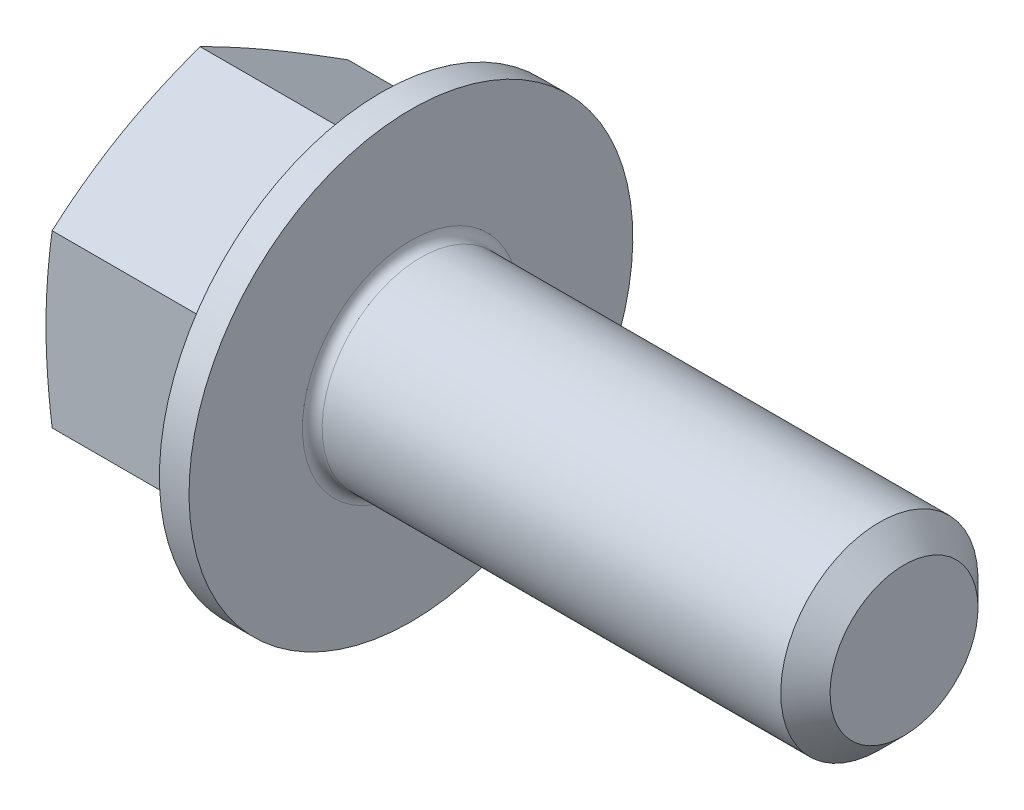
SolidWorks part; units mm, degrees
ref_plane "Front Plane" through (0, 0, 0) normal (0, 0, 1) x (1, 0, 0)
ref_plane "Top Plane" through (0, 0, 0) normal (0, 1, 0) x (1, 0, 0)
ref_plane "Right Plane" through (0, 0, 0) normal (1, 0, 0) x (0, 0, -1)
sketch "Sketch1" plane through (0, 0, 0) normal (0, 0, 1) x (1, 0, 0)
  line L0 (0, 0) -> (5, 0) construction
  line L1 (0, 0) -> (-2.2, 0) construction
  line L2 (0.1, 1) -> (4.75, 1)
  line L3 (5, 0) -> (5, 0.75)
  line L4 (0, 1.1) -> (0, 2.25)
  line L5 (0, 2.25) -> (-0.3, 2.25)
  line L6 (-0.3, 2.25) -> (-0.501, 1.5)
  line L7 (-0.501, 1.5) -> (-2.2, 1.5)
  line L8 (-2.2, 1.5) -> (-2.2, 1.2)
  line L9 (-2.2, 1.2) -> (-1.925, 1.2)
  line L10 (-1.925, 1.2) -> (-1.925, 0)
  line L11 (-1.925, 0) -> (5, 0)
  line L12 (-1.925, 0) -> (-1.925, 1.58) construction
  line L14 (5, 0.75) -> (4.75, 1)
  line L15 (5, 0) -> (0.4, 0) construction
  arc A0 (0.1, 1) -> (0, 1.1) centre (0.1, 1.1) cw
  dimension "D7" = 0.1
  dimension "L" = 5
  dimension "K" = 2.2
  dimension "s" = 3
  dimension "dia" = 2
  dimension "D1" = 2.4
  dimension "D2" = 0.275
  dimension "c" = 0.3
  dimension "D4" = 15
  dimension "D5" = 45
  dimension "min" = 1.5
  dimension "B" = 4.6
  dimension "Dc" = 4.5
revolve "Revolve1" add sketch "Sketch1" angle 360 about L11
cosmetic thread "Cosmetic Thread1" [suppressed] parameters "D1"=4.25, "D2"=1.5
sketch "Sketch2" plane through (-2.2, 0, 0) normal (-1, 0, 0) x (0, 0, 1)
  line L1 (0, 1.7321) -> (-1.5, 0.866)
  line L2 (-1.5, 0.866) -> (-1.5, -0.866)
  line L3 (-1.5, -0.866) -> (0, -1.7321)
  line L4 (0, -1.7321) -> (1.5, -0.866)
  line L5 (1.5, -0.866) -> (1.5, 0.866)
  line L6 (1.5, 0.866) -> (0, 1.7321)
  circle A0 centre (0, 0) radius 1.2 construction
  circle A1 centre (0, 0) radius 1.2
  circle A2 centre (0, 0) radius 1.5 construction
  circle A3 centre (0, 0) radius 1.5 construction
extrude "Extrude1" add sketch "Sketch2" against normal up to next (2.2 mm away)
sketch "Sketch3" plane through (0, 0, 0) normal (0, 1, 0) x (1, 0, 0)
  line L0 (-2.401, 0.75) -> (-1.999, 2.25)
  line L1 (-2.2, 0) -> (-2.2, 1.5) construction
  line L2 (0, 0) -> (-3.6033, 0) construction
  line L3 (-1.999, 2.25) -> (-2.401, 2.25)
  line L4 (-2.401, 2.25) -> (-2.401, 0.75)
  dimension "D1" = 15
  dimension "D2" = 1.5
revolve "Cut-Revolve1" cut sketch "Sketch3" angle 360 about L2
fillet "Fillet1" radius 0.1 6 edges
sketch "Sketch4" plane through (0, 0, 0) normal (0, 0, 1) x (1, 0, 0)
  line L0 (0, 0) -> (5.3731, 0) construction
  line L1 (5, -0.75) -> (5, 0.75) construction
  line L3 (5, 0.665) -> (4.1912, 1)
  line L4 (0.1, 1) -> (4.75, 1) construction
  line L5 (4.1912, 1) -> (4.1912, 1.5)
  line L6 (4.1912, 1.5) -> (5, 1.5)
  line L7 (5, 1.5) -> (5, 0.665)
  dimension "D1" = 0.5
  dimension "D2" = 22.5
  dimension "Dp" = 1.33
revolve "Cut-Revolve2" [suppressed] cut sketch "Sketch4" angle 360 about L0
sketch "Sketch5" plane through (0, 0, 0) normal (0, 0, 1) x (1, 0, 0)
  line L0 (5, 0) -> (0.75, 0) construction
  line L1 (-1.925, 0) -> (5, 0) construction
  line L2 (0.8943, 0.75) -> (1.0387, 1)
  line L3 (1.0387, 1) -> (1.0387, 1.2887)
  line L4 (1.0387, 1.2887) -> (0.75, 1.2887)
  line L5 (0.75, 1.2887) -> (0.75, 1)
  line L6 (0.75, 1) -> (0.8943, 0.75)
  dimension "B" = 4.25
  dimension "D1" = 1.5
  dimension "D2" = 2
revolve "Cut-Revolve10" [suppressed] cut sketch "Sketch5" angle 360 about L0
pattern_linear "LPattern10" [suppressed] count 11 spacing 0.4 along (1, 0, 0) of bodies 111
equation "\"D1@Sketch1\" = \"s@Sketch1\" / 10 * 8"
equation "\"D2@Sketch1\" = \"K@Sketch1\" / 8"
equation "\"D2@Sketch3\" = \"s@Sketch1\" / 2"
equation "\"D2@Cosmetic Thread1\" = \"min@Sketch1\""
equation "\"D1@Cosmetic Thread1\" = \"B@Sketch1\" -  ( \"dia@Sketch1\" - \"min@Sketch1\" )  / 2 - \"D7@Sketch1\""
equation "\"D1@Sketch5\" = \"D2@Cosmetic Thread1\""
equation "\"D2@Sketch5\" = \"dia@Sketch1\""
equation "\"B@Sketch5\" = \"D1@Cosmetic Thread1\""
equation "\"D1@LPattern10\" = int( \"D1@Cosmetic Thread1\" / \"D3@LPattern10\" + 0.999 ) "
